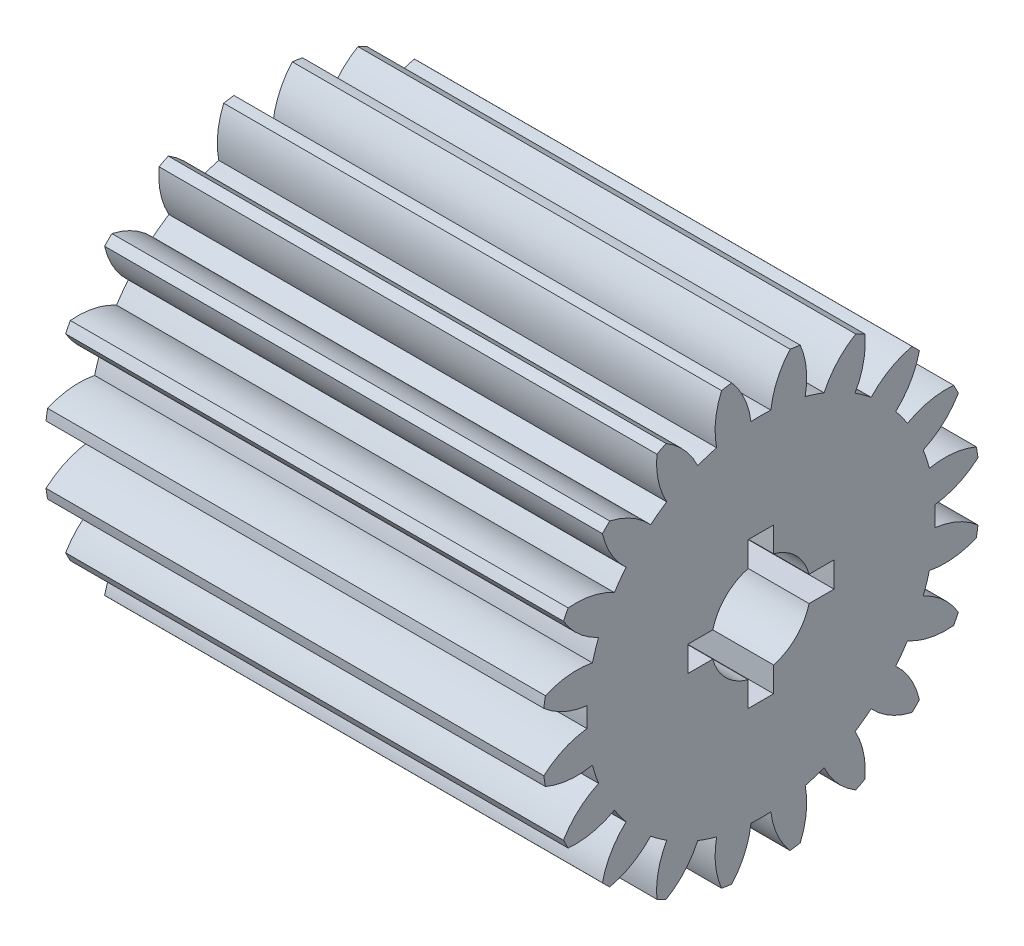
SolidWorks part; units mm, degrees
material "AISI 1020"
ref_plane "Plane1" through (0, 0, 0) normal (0, 0, 1) x (1, 0, 0)
ref_plane "Plane2" through (0, 0, 0) normal (0, 1, 0) x (1, 0, 0)
ref_plane "Plane3" through (0, 0, 0) normal (1, 0, 0) x (0, 0, -1)
other "Configuration Table"
sketch "HoldingSke" plane through (0, 0, 0) normal (0, 1, 0) x (1, 0, 0)
  line L0 (0, 0) -> (2.3492, -0.8551)
  line L1 (-15, 0) -> (100, 0) construction
  line L2 (0, 0) -> (-2.1039, 2.3779)
  line L3 (0, 0) -> (-11.863, 4.5341)
  line L4 (0, 0) -> (8.1152, 2.9537)
  line L5 (0, 0) -> (-46.8476, -17.4728)
  line L6 (0, 0) -> (-8.2896, -5.593)
  line L7 (-2.1039, 2.3779) -> (8.6586, 51.2059)
  line L8 (-76.2, 54.61) -> (-75.9, 54.61)
  line L9 (-71.009, 38.7566) -> (-53.1078, 45.2721)
  line L10 (-76.2, 71.12) -> (104.1128, 71.12)
  line L11 (0, 0) -> (-10, 0)
  line L12 (-76.2, 101.6) -> (-76.185, 101.6)
  line L13 (24.9733, 27.94) -> (52.9518, 28.4284)
  line L14 (24.9733, 27.94) -> (24.9743, 27.94)
  line L15 (24.9733, 27.94) -> (100.4006, 29.5858)
  line L16 (-63.627, -0.4) -> (-12.827, -0.4)
  circle A0 centre (0, 0) radius 1
  circle A1 centre (0, 0) radius 3.499
  circle A2 centre (0, 0) radius 37.5
  circle A3 centre (0, 0) radius 1
  dimension "Num_teeth" = 20
  dimension "Pitch_radius" = 180.3128
  dimension "Width" = 10
  dimension "Thickness" = 10
sketch "BasProSke" plane through (0, 0, 0) normal (0, 1, 0) x (1, 0, 0)
  line L0 (-10, 0) -> (60, 0) construction
  line L1 (0, 0) -> (0, 4.4)
  line L2 (0, 0) -> (10, 0)
  line L3 (10, 0) -> (10, 4.4)
  line L4 (10, 4.4) -> (0, 4.4)
  dimension "Thickness" = 10
  dimension "Diameter" = 8.8
revolve "Base-Revolve" add sketch "BasProSke" angle 360 about L0
sketch "TooCutSke" plane through (0, 0, 0) normal (1, 0, 0) x (0, 0, -1)
  line L1 (0, 0) -> (0, 107) construction
  line L2 (0, 0) -> (-0.3401, 3.9855) construction
  line L3 (0, 0) -> (-1.2482, 7.8811) construction
  line L4 (-0.3401, 3.9855) -> (-0.6241, 3.9405) construction
  arc A0 (0.1996, 3.4933) -> (-0.1996, 3.4933) centre (0, 0) ccw
  arc A1 (0.606, 4.3837) -> (-0.606, 4.3837) centre (0, 0) ccw
  circle A2 centre (0, 0) radius 4 construction
  circle A3 centre (0, 0) radius 3.7588 construction
  arc A4 (-0.1996, 3.4933) -> (-0.606, 4.3837) centre (-1.7886, 3.306) ccw
  arc A5 (0.606, 4.3837) -> (0.1996, 3.4933) centre (1.7886, 3.306) ccw
extrude "ToothCut" cut sketch "TooCutSke" along normal through all
fillet "Breaks" [suppressed] radius 0.008 tangent propagation no
fillet "RootFillets" [suppressed] radius 0.101
pattern_circular "TeethCuts" count 20 every 18 about axis through (-10, 0, 0) along (1, 0, 0) of "ToothCut", "Breaks", "RootFillets"
sketch "HubNeaOneSke" plane through (0, 0, 0) normal (-1, 0, 0) x (0, 0, 1)
  circle A0 centre (0, 0) radius 3.499
  dimension "Diameter" = 6.998
extrude "HubNearOne" [suppressed] add sketch "HubNeaOneSke" along normal blind 40.0001
sketch "HubNeaBotSke" plane through (0, 0, 0) normal (-1, 0, 0) x (0, 0, 1)
  circle A0 centre (0, 0) radius 3.499
  dimension "Diameter" = 6.998
extrude "HubNearBoth" [suppressed] add sketch "HubNeaBotSke" along normal blind 20
ref_plane "FarPln" through (10, 0, 0) normal (1, 0, 0) x (0, 0, -1)
sketch "HubFarSke" plane through (10, 0, 0) normal (1, 0, 0) x (0, 0, -1)
  circle A0 centre (0, 0) radius 3.499
  dimension "Diameter" = 6.998
extrude "HubFar" [suppressed] add sketch "HubFarSke" along normal blind 20
sketch "BorSke" plane through (0, 0, 0) normal (1, 0, 0) x (0, 0, -1)
  circle A0 centre (0, 0) radius 1
  dimension "Diameter" = 2
extrude "Bore" cut sketch "BorSke" along normal mid plane 100.0001
sketch "KeySke" plane through (0, 0, 0) normal (1, 0, 0) x (0, 0, -1)
  line L0 (-0.4, 0) -> (-0.4, 1.3)
  line L1 (-0.4, 1.3) -> (0.4, 1.3)
  line L2 (0.4, 1.3) -> (0.4, 0)
  line L3 (0, 0) -> (0, 34) construction
  line L4 (-0.4, 0) -> (0.4, 0)
  dimension "Width" = 0.8
extrude "Keyway" [suppressed] cut sketch "KeySke" along normal mid plane 100.0001
pattern_circular "Keyway2" [suppressed] count 2 every 90 about axis through (-10, 0, 0) along (1, 0, 0) reverse direction yes
sketch "Sketch1" plane through (10, 0, 0) normal (1, 0, 0) x (0, 0, -1)
  line L0 (-0.255, 0.9587) -> (0.255, 0.9587)
  line L1 (-0.255, 0.9587) -> (-0.255, 1.4687)
  line L2 (0.255, 0.9587) -> (0.255, 1.4687)
  line L3 (-0.255, 1.4687) -> (0.255, 1.4687)
  line L4 (0.9587, 0.255) -> (0.9587, -0.255)
  line L5 (0.9587, 0.255) -> (1.4687, 0.255)
  line L6 (0.9587, -0.255) -> (1.4687, -0.255)
  line L7 (1.4687, 0.255) -> (1.4687, -0.255)
  line L8 (0.255, -0.9587) -> (-0.255, -0.9587)
  line L9 (0.255, -0.9587) -> (0.255, -1.4687)
  line L10 (-0.255, -0.9587) -> (-0.255, -1.4687)
  line L11 (0.255, -1.4687) -> (-0.255, -1.4687)
  line L12 (-0.9587, -0.255) -> (-0.9587, 0.255)
  line L13 (-0.9587, -0.255) -> (-1.4687, -0.255)
  line L14 (-0.9587, 0.255) -> (-1.4687, 0.255)
  line L15 (-1.4687, -0.255) -> (-1.4687, 0.255)
  circle A0 centre (0, 0) radius 0.992
  dimension "D2" = 1.984
  dimension "D1" = 0.51
  dimension "D3" = 0.51
  dimension "D4" = 0.51
  dimension "D5" = 0.51
  dimension "D6" = 0.51
  dimension "D7" = 0.51
  dimension "D8" = 0.51
  dimension "D9" = 0.51
extrude "Cut-Extrude1" cut sketch "Sketch1" against normal blind 100 contours L3 L2 L0 L1 | L5 L7 L6 L4 | L9 L11 L10 L8 | L13 L15 L14 L12
equation "' \"Module@HoldingSke\" = 6.35"
equation "' \"Num_teeth@HoldingSke\" = 12"
equation "' \"Ap@HoldingSke\" =  20"
equation "' \"Ap@HoldingSke\" = 20"
equation "' \"Width@HoldingSke\" = 0.5 * 25.4"
equation "' \"Hub_dia@HoldingSke\"= 1 * 25.4"
equation "' \"Hub_dia@HoldingSke\" = 1 * 25.4"
equation "' \"Overall_len@HoldingSke\" = 1.0 * 25.4"
equation "' \"Bore@HoldingSke\" = 0.75 * 25.4"
equation "' \"T_dim@HoldingSke\" = 0.1 * 25.4"
equation "' \"Width@KeySke\" = 0.25 * 25.4"
equation "' \"Show_teeth@HoldingSke\" = 13"
equation "' \"Backlash@HoldingSke\" = 0.009 * 25.4"
equation "' \"Addendum_fac@HoldingSke\" = 1.0"
equation "' \"Dedendum_fac@HoldingSke\" = 1.25"
equation "' \"Dedendum_add@HoldingSke\" = 0.00005 * 25.4"
equation "' \"Clearance_fac@HoldingSke\" = 0.25"
equation "\"Pitch@HoldingSke\" = 1 / \"Module@HoldingSke\""
equation "\"Overcut_dia@TooCutSke\" = (\"Num_teeth@HoldingSke\" + 2 * \"Addendum_fac@HoldingSke\") / \"Pitch@HoldingSke\" + 0.002 * 25.4"
equation "\"Pitch_dia@TooCutSke\" = \"Num_teeth@HoldingSke\" / \"Pitch@HoldingSke\""
equation "\"Base_dia@TooCutSke\" = \"Num_teeth@HoldingSke\" / \"Pitch@HoldingSke\" * cos((\"Ap@HoldingSke\"  * 3.14159265 / 180))"
equation "\"Root_dia@TooCutSke\" = (\"Num_teeth@HoldingSke\" + 2) / \"Pitch@HoldingSke\" - 2 * (\"Addendum_fac@HoldingSke\" + \"Dedendum_fac@HoldingSke\") / \"Pitch@HoldingSke\" - \"Dedendum_add@HoldingSke\" * 2"
equation "\"Half_ang@TooCutSke\" = 180 / \"Num_teeth@HoldingSke\""
equation "\"Half_CT@TooCutSke\" = \"Num_teeth@HoldingSke\" / \"Pitch@HoldingSke\" * sin((3.14159265 / 2 / \"Num_teeth@HoldingSke\")) / 2 - 7 * \"Backlash@HoldingSke\" / 4"
equation "\"Flank_rad@TooCutSke\" = \"Num_teeth@HoldingSke\" / \"Pitch@HoldingSke\" / 5"
equation "\"Radius@RootFillets\" = \"Clearance_fac@HoldingSke\" / \"Pitch@HoldingSke\" + \"Dedendum_add@HoldingSke\""
equation "\"Break_rad@Breaks\" = 0.02 / \"Pitch@HoldingSke\""
equation "\"Thickness@HoldingSke\" = \"Width@HoldingSke\""
equation "\"OAL@HoldingSke\" = \"Thickness@HoldingSke\""
equation "\"MHD@HoldingSke\" = (\"Num_teeth@HoldingSke\" + 2) / \"Pitch@HoldingSke\" - 2 * (\"Addendum_fac@HoldingSke\" + \"Dedendum_fac@HoldingSke\")  / \"Pitch@HoldingSke\" - \"Dedendum_add@HoldingSke\" * 2"
equation "\"MBD@HoldingSke\" = (\"Num_teeth@HoldingSke\" + 2) / \"Pitch@HoldingSke\" - 2 * (\"Addendum_fac@HoldingSke\" + \"Dedendum_fac@HoldingSke\")  / \"Pitch@HoldingSke\" - \"Dedendum_add@HoldingSke\" * 2 - 0.002 * 25.4"
equation "\"MHD@HoldingSke\" = ((sgn( \"MHD@HoldingSke\" - \"Hub_dia@HoldingSke\" )-1)*( \"MHD@HoldingSke\" - \"Hub_dia@HoldingSke\" ))/-2+ \"Hub_dia@HoldingSke\""
equation "\"MBD@HoldingSke\" = ((sgn( \"MBD@HoldingSke\" - \"Bore@HoldingSke\" )-1)*( \"MBD@HoldingSke\" - \"Bore@HoldingSke\" ))/-2+ \"Bore@HoldingSke\""
equation "\"OAL@HoldingSke\" = ((sgn( \"OAL@HoldingSke\" - \"Overall_len@HoldingSke\" )+1)*( \"OAL@HoldingSke\" - \"Overall_len@HoldingSke\" ))/2 + \"Overall_len@HoldingSke\" + 0.000002 * 25.4"
equation "\"Num_teeth@TeethCuts\" = int( \"Show_teeth@HoldingSke\" ) + 1"
equation "\"Num_teeth@TeethCuts\" = ((sgn( \"Num_teeth@TeethCuts\" - \"Num_teeth@HoldingSke\" )-1)*( \"Num_teeth@TeethCuts\" - \"Num_teeth@HoldingSke\" ))/-2+ \"Num_teeth@HoldingSke\""
equation "\"Num_teeth@TeethCuts\" = ((sgn( \"Num_teeth@TeethCuts\" - 2.0)+1)*( \"Num_teeth@TeethCuts\" - 2.0))/2 +2.0"
equation "\"Angle@TeethCuts\" = 360.0 / \"Num_teeth@HoldingSke\""
equation "\"Diameter@BasProSke\" = (\"Num_teeth@HoldingSke\" + 2 * \"Addendum_fac@HoldingSke\") / \"Pitch@HoldingSke\""
equation "\"Thickness@BasProSke\"  = \"Thickness@HoldingSke\""
equation "' \"Fillet_rad@BasProSke\" =  \"Thickness@HoldingSke\" * 0.05"
equation "' \"Fillet_rad@BasProSke\" = \"Thickness@HoldingSke\" * 0.05"
equation "\"MHD@HoldingSke\" = ((sgn( \"MHD@HoldingSke\" - \"Root_dia@TooCutSke\" )-1)*( \"MHD@HoldingSke\" - \"Root_dia@TooCutSke\" ))/-2+ \"Root_dia@TooCutSke\""
equation "\"Diameter@HubNeaOneSke\" = \"MHD@HoldingSke\""
equation "\"Length@HubNearOne\" = \"OAL@HoldingSke\" - \"Thickness@BasProSke\""
equation "\"Diameter@HubNeaBotSke\" = \"MHD@HoldingSke\""
equation "\"Length@HubNearBoth\" = ( \"OAL@HoldingSke\" - \"Thickness@BasProSke\" ) / 2.0"
equation "\"Thickness@FarPln\" = \"Thickness@BasProSke\""
equation "\"Diameter@HubFarSke\" = \"MHD@HoldingSke\""
equation "\"Length@HubFar\" = ( \"OAL@HoldingSke\" - \"Thickness@BasProSke\" ) / 2.0"
equation "\"Diameter@BorSke\" = \"MBD@HoldingSke\""
equation "\"D1@Bore\" = \"OAL@HoldingSke\" * 2.0"
equation "\"D1@Keyway\" = \"OAL@HoldingSke\" * 2.0"
equation "\"Offset@KeySke\" = \"T_dim@HoldingSke\" + \"MBD@HoldingSke\" / 2.0"
